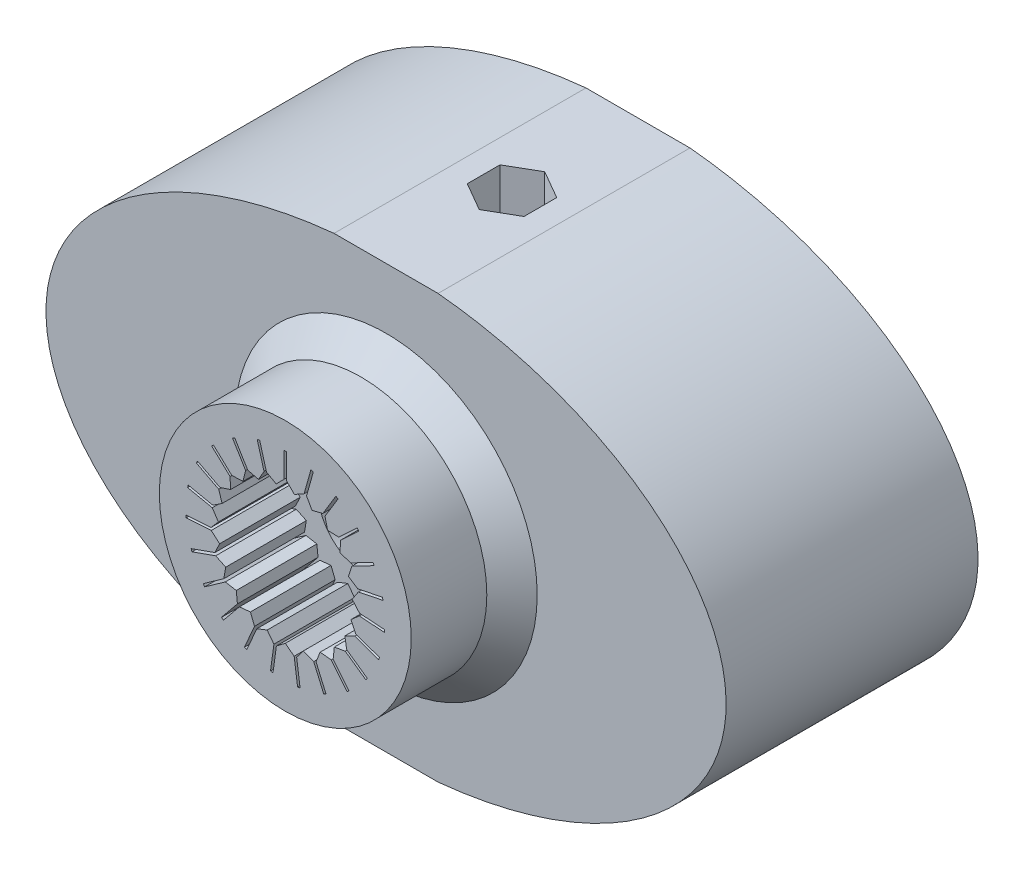
SolidWorks part; units mm, degrees
ref_plane "正面" through (0, 0, 0) normal (0, 0, 1) x (1, 0, 0)
ref_plane "平面" through (0, 0, 0) normal (0, 1, 0) x (1, 0, 0)
ref_plane "右側面" through (0, 0, 0) normal (1, 0, 0) x (0, 0, -1)
sketch "ｽｹｯﾁ1" plane through (0, 0, 0) normal (0, 0, 1) x (1, 0, 0)
  ellipse E0 centre (0, 0) end of major axis (-13.5, 0) minor radius 8.5
  dimension "D1" = 13.5
  dimension "D2" = 8.5
extrude "ﾎﾞｽ - 押し出し1" add sketch "ｽｹｯﾁ1" along normal blind 10
sketch "ｽｹｯﾁ2" plane through (0, 0, 0) normal (0, 1, 0) x (1, 0, 0)
  line L1 (2.5, -13.2881) -> (-2.5, -13.2881)
  line L2 (2.5, -13.2881) -> (2.5, 3.6993)
  line L3 (2.5, 3.6993) -> (-2.5, 3.6993)
  line L4 (-2.5, -13.2881) -> (-2.5, 3.6993)
  line L5 (2.5, -13.2881) -> (-2.5, 3.6993) construction
  line L6 (2.5, 3.6993) -> (-2.5, -13.2881) construction
  point P0 (0, -4.7944)
  dimension "D1" = 5
extrude "ｶｯﾄ - 押し出し2" cut sketch "ｽｹｯﾁ2" against normal blind 10 from offset 18.4
mirror "ﾐﾗｰ1" about plane through (0, 0, 0) normal (0, 1, 0) of "ｶｯﾄ - 押し出し2"
sketch "ｽｹｯﾁ3" plane through (0, 8.4, 0) normal (0, 1, 0) x (1, 0, 0)
  line L2 (2.0647, -10) -> (2.0647, 0) construction
  line L3 (1.1258, -5.65) -> (1.1258, -4.35)
  line L4 (1.1258, -4.35) -> (0, -3.7)
  line L5 (0, -3.7) -> (-1.1258, -4.35)
  line L6 (-1.1258, -4.35) -> (-1.1258, -5.65)
  line L7 (-1.1258, -5.65) -> (0, -6.3)
  line L8 (0, -6.3) -> (1.1258, -5.65)
  circle A1 centre (0, -5) radius 1.1258 construction
  point P16 (2.0647, -5)
  point P18 (0, 0)
  dimension "D1" = 2.6
extrude "ｶｯﾄ - 押し出し3" cut sketch "ｽｹｯﾁ3" against normal through all both and the other way through all
sketch "ｽｹｯﾁ6" plane through (0, 0, 10) normal (0, 0, 1) x (1, 0, 0)
  circle A0 centre (0, 0) radius 5
  dimension "D1" = 10
extrude "ﾎﾞｽ - 押し出し3" add sketch "ｽｹｯﾁ6" along normal blind 4
sketch "ｽｹｯﾁ5" plane through (0, 0, 14) normal (0, 0, 1) x (1, 0, 0)
  line L0 (-0.3625, 2.6375) -> (0, 3) construction
  line L1 (0, 3) -> (0.3625, 2.6375) construction
  line L2 (-0.3625, 2.6375) -> (0, 0) construction
  line L3 (0, 0) -> (0.3625, 2.6375) construction
  line L4 (0, 3) -> (0, 0) construction
  line L5 (-0.05, 2.95) -> (-0.05, 3.95)
  line L6 (-0.05, 3.95) -> (0.05, 3.95)
  line L7 (0.05, 3.95) -> (0.05, 2.95)
  line L8 (-0.05, 2.95) -> (0.05, 2.95) construction
  line L9 (-0.3625, 2.6375) -> (-0.05, 2.95)
  line L10 (-0.05, 2.95) -> (0.05, 2.95) construction
  line L11 (0.3625, 2.6375) -> (0.05, 2.95)
  line L12 (0.3625, 2.6375) -> (0.7478, 2.8541)
  line L13 (0.7478, 2.8541) -> (1.0176, 3.817)
  line L14 (1.1138, 3.79) -> (0.844, 2.8271)
  line L15 (1.0607, 2.4419) -> (0.844, 2.8271)
  line L16 (1.0176, 3.817) -> (1.1138, 3.79)
  line L17 (1.0607, 2.4419) -> (1.4901, 2.5465)
  line L18 (1.4901, 2.5465) -> (2.0096, 3.4009)
  line L19 (2.0951, 3.349) -> (1.5755, 2.4946)
  line L20 (1.6801, 2.0652) -> (1.5755, 2.4946)
  line L21 (2.0096, 3.4009) -> (2.0951, 3.349)
  line L22 (1.6801, 2.0652) -> (2.1218, 2.0501)
  line L23 (2.1218, 2.0501) -> (2.8527, 2.7326)
  line L24 (2.9209, 2.6595) -> (2.1901, 1.977)
  line L25 (2.175, 1.5353) -> (2.1901, 1.977)
  line L26 (2.8527, 2.7326) -> (2.9209, 2.6595)
  line L27 (2.175, 1.5353) -> (2.5963, 1.4016)
  line L28 (2.5963, 1.4016) -> (3.4841, 1.8617)
  line L29 (3.5301, 1.7729) -> (2.6423, 1.3128)
  line L30 (2.5086, 0.8915) -> (2.6423, 1.3128)
  line L31 (3.4841, 1.8617) -> (3.5301, 1.7729)
  line L32 (2.5086, 0.8915) -> (2.8781, 0.6491)
  line L33 (2.8781, 0.6491) -> (3.8572, 0.8526)
  line L34 (3.8776, 0.7547) -> (2.8985, 0.5512)
  line L35 (2.6561, 0.1817) -> (2.8985, 0.5512)
  line L36 (3.8572, 0.8526) -> (3.8776, 0.7547)
  line L37 (2.6561, 0.1817) -> (2.9465, -0.1514)
  line L38 (2.9465, -0.1514) -> (3.9442, -0.2197)
  line L39 (3.9374, -0.3194) -> (2.9397, -0.2512)
  line L40 (2.6066, -0.5417) -> (2.9397, -0.2512)
  line L41 (3.9442, -0.2197) -> (3.9374, -0.3194)
  line L42 (2.6066, -0.5417) -> (2.7964, -0.9408)
  line L43 (2.7964, -0.9408) -> (3.7387, -1.2757)
  line L44 (3.7052, -1.3699) -> (2.7629, -1.035)
  line L45 (2.3638, -1.2248) -> (2.7629, -1.035)
  line L46 (3.7387, -1.2757) -> (3.7052, -1.3699)
  line L47 (2.3638, -1.2248) -> (2.4389, -1.6604)
  line L48 (2.4389, -1.6604) -> (3.2559, -2.237)
  line L49 (3.1982, -2.3187) -> (2.3812, -1.7421)
  line L50 (1.9457, -1.8171) -> (2.3812, -1.7421)
  line L51 (3.2559, -2.237) -> (3.1982, -2.3187)
  line L52 (1.9457, -1.8171) -> (1.9005, -2.2568)
  line L53 (1.9005, -2.2568) -> (2.5316, -3.0325)
  line L54 (2.454, -3.0956) -> (1.8229, -2.3199)
  line L55 (1.3833, -2.2747) -> (1.8229, -2.3199)
  line L56 (2.5316, -3.0325) -> (2.454, -3.0956)
  line L57 (1.3833, -2.2747) -> (1.2211, -2.6859)
  line L58 (1.2211, -2.6859) -> (1.6195, -3.6031)
  line L59 (1.5278, -3.6429) -> (1.1294, -2.7257)
  line L60 (0.7183, -2.5636) -> (1.1294, -2.7257)
  line L61 (1.6195, -3.6031) -> (1.5278, -3.6429)
  line L62 (0.7183, -2.5636) -> (0.4512, -2.9157)
  line L63 (0.4512, -2.9157) -> (0.5874, -3.9064)
  line L64 (0.4883, -3.92) -> (0.3522, -2.9293)
  line L65 (0, -2.6623) -> (0.3522, -2.9293)
  line L66 (0.5874, -3.9064) -> (0.4883, -3.92)
  line L67 (0, -2.6623) -> (-0.3522, -2.9293)
  line L68 (-0.3522, -2.9293) -> (-0.4883, -3.92)
  line L69 (-0.5874, -3.9064) -> (-0.4512, -2.9157)
  line L70 (-0.7183, -2.5636) -> (-0.4512, -2.9157)
  line L71 (-0.4883, -3.92) -> (-0.5874, -3.9064)
  line L72 (-0.7183, -2.5636) -> (-1.1294, -2.7257)
  line L73 (-1.1294, -2.7257) -> (-1.5278, -3.6429)
  line L74 (-1.6195, -3.6031) -> (-1.2211, -2.6859)
  line L75 (-1.3833, -2.2747) -> (-1.2211, -2.6859)
  line L76 (-1.5278, -3.6429) -> (-1.6195, -3.6031)
  line L77 (-1.3833, -2.2747) -> (-1.8229, -2.3199)
  line L78 (-1.8229, -2.3199) -> (-2.454, -3.0956)
  line L79 (-2.5316, -3.0325) -> (-1.9005, -2.2568)
  line L80 (-1.9457, -1.8171) -> (-1.9005, -2.2568)
  line L81 (-2.454, -3.0956) -> (-2.5316, -3.0325)
  line L82 (-1.9457, -1.8171) -> (-2.3812, -1.7421)
  line L83 (-2.3812, -1.7421) -> (-3.1982, -2.3187)
  line L84 (-3.2559, -2.237) -> (-2.4389, -1.6604)
  line L85 (-2.3638, -1.2248) -> (-2.4389, -1.6604)
  line L86 (-3.1982, -2.3187) -> (-3.2559, -2.237)
  line L87 (-2.3638, -1.2248) -> (-2.7629, -1.035)
  line L88 (-2.7629, -1.035) -> (-3.7052, -1.3699)
  line L89 (-3.7387, -1.2757) -> (-2.7964, -0.9408)
  line L90 (-2.6066, -0.5417) -> (-2.7964, -0.9408)
  line L91 (-3.7052, -1.3699) -> (-3.7387, -1.2757)
  line L92 (-2.6066, -0.5417) -> (-2.9397, -0.2512)
  line L93 (-2.9397, -0.2512) -> (-3.9374, -0.3194)
  line L94 (-3.9442, -0.2197) -> (-2.9465, -0.1514)
  line L95 (-2.6561, 0.1817) -> (-2.9465, -0.1514)
  line L96 (-3.9374, -0.3194) -> (-3.9442, -0.2197)
  line L97 (-2.6561, 0.1817) -> (-2.8985, 0.5512)
  line L98 (-2.8985, 0.5512) -> (-3.8776, 0.7547)
  line L99 (-3.8572, 0.8526) -> (-2.8781, 0.6491)
  line L100 (-2.5086, 0.8915) -> (-2.8781, 0.6491)
  line L101 (-3.8776, 0.7547) -> (-3.8572, 0.8526)
  line L102 (-2.5086, 0.8915) -> (-2.6423, 1.3128)
  line L103 (-2.6423, 1.3128) -> (-3.5301, 1.7729)
  line L104 (-3.4841, 1.8617) -> (-2.5963, 1.4016)
  line L105 (-2.175, 1.5353) -> (-2.5963, 1.4016)
  line L106 (-3.5301, 1.7729) -> (-3.4841, 1.8617)
  line L107 (-2.175, 1.5353) -> (-2.1901, 1.977)
  line L108 (-2.1901, 1.977) -> (-2.9209, 2.6595)
  line L109 (-2.8527, 2.7326) -> (-2.1218, 2.0501)
  line L110 (-1.6801, 2.0652) -> (-2.1218, 2.0501)
  line L111 (-2.9209, 2.6595) -> (-2.8527, 2.7326)
  line L112 (-1.6801, 2.0652) -> (-1.5755, 2.4946)
  line L113 (-1.5755, 2.4946) -> (-2.0951, 3.349)
  line L114 (-2.0096, 3.4009) -> (-1.4901, 2.5465)
  line L115 (-1.0607, 2.4419) -> (-1.4901, 2.5465)
  line L116 (-2.0951, 3.349) -> (-2.0096, 3.4009)
  line L117 (-1.0607, 2.4419) -> (-0.844, 2.8271)
  line L118 (-0.844, 2.8271) -> (-1.1138, 3.79)
  line L119 (-1.0176, 3.817) -> (-0.7478, 2.8541)
  line L120 (-0.3625, 2.6375) -> (-0.7478, 2.8541)
  line L121 (-1.1138, 3.79) -> (-1.0176, 3.817)
  circle A0 centre (0, 0) radius 3 construction
  circle A1 centre (0, 0) radius 2.6623 construction
  point P147 (0, 0)
  dimension "D1" = 6
  dimension "D2" = 7.826
  dimension "D3" = 7.826
  dimension "D4" = 0.1
  dimension "D5" = 1
  dimension "D6" = 23
extrude "ｶｯﾄ - 押し出し5" cut sketch "ｽｹｯﾁ5" against normal blind 3.2
chamfer "面取り1" distance 1 angle 45 1 edges at (5, 0, 10)
sketch "ｽｹｯﾁ7" plane through (0, 0, 10.8) normal (0, 0, 1) x (1, 0, 0)
  circle A0 centre (0, 0) radius 1.9
  dimension "D1" = 3.8
extrude "ｶｯﾄ - 押し出し6" cut sketch "ｽｹｯﾁ7" against normal through all
sketch "ｽｹｯﾁ8" plane through (0, 0, 0) normal (0, 0, -1) x (-1, 0, 0)
  circle A0 centre (0, 0) radius 3
  dimension "D1" = 6
extrude "ｶｯﾄ - 押し出し7" cut sketch "ｽｹｯﾁ8" against normal blind 6
equation "\"18.4.300mm\"=18.3"
equation "\"D2@ｽｹｯﾁ5\"=360deg/46"
equation "\"D3@ｽｹｯﾁ5\"=\"D2@ｽｹｯﾁ5\""
